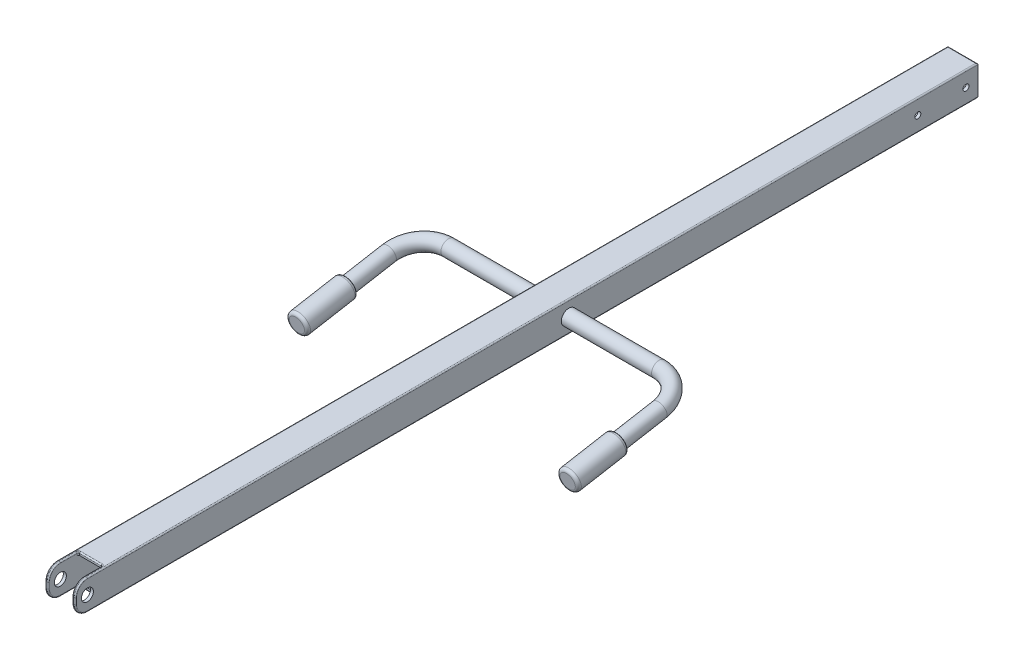
SolidWorks part; units mm, degrees
ref_plane "前视基准面" through (0, 0, 0) normal (0, 0, 1) x (1, 0, 0)
ref_plane "上视基准面" through (0, 0, 0) normal (0, 1, 0) x (1, 0, 0)
ref_plane "右视基准面" through (0, 0, 0) normal (1, 0, 0) x (0, 0, -1)
other "Configuration Table"
sketch "草图1" plane through (0, 0, 0) normal (0, 0, 1) x (1, 0, 0)
  line L1 (-25, 25) -> (25, 25)
  line L2 (-25, 25) -> (-25, -25)
  line L3 (-25, -25) -> (25, -25)
  line L4 (25, 25) -> (25, -25)
  line L5 (-25, 25) -> (25, -25) construction
  line L6 (-25, -25) -> (25, 25) construction
  point P4 (0, 0)
  dimension "D1" = 50
  dimension "D2" = 50
extrude "拉伸-薄壁1" add sketch "草图1" along normal blind 1500 thin thin type one direction reverse wall 5
sketch "草图2" plane through (25, 0, 0) normal (1, 0, 0) x (0, 0, -1)
  line L0 (0, 0) -> (-1500, 0) construction
  line L1 (0, -25) -> (0, 25) construction
  line L2 (-1500, -25) -> (-1500, 25) construction
  line L3 (-1500, 20) -> (-1500, -20) construction
  circle A0 centre (-20, 0) radius 5
  circle A1 centre (-100, 0) radius 5
  circle A2 centre (-1480, 0) radius 10
  dimension "D1" = 10
  dimension "D2" = 20
  dimension "D3" = 80
  dimension "D4" = 20
  dimension "D5" = 20
extrude "切除-拉伸1" cut sketch "草图2" against normal through all
sketch "草图4" plane through (0, 25, 0) normal (0, 1, 0) x (1, 0, 0)
  line L0 (0, -1500) -> (0, -1466.8151) construction
  line L1 (25, -1500) -> (-25, -1500) construction
  line L2 (-25, -1500) -> (-25, 0) construction
  line L3 (20, -1500) -> (-20, -1500)
  line L4 (20, -1500) -> (20, -1450)
  line L5 (20, -1450) -> (-20, -1450)
  line L6 (-20, -1500) -> (-20, -1450)
  line L7 (20, -1500) -> (-20, -1450) construction
  line L8 (20, -1450) -> (-20, -1500) construction
  line L9 (25, -1500) -> (25, 0) construction
  point P8 (0, -1475)
  dimension "D1" = 5
  dimension "D2" = 5
  dimension "D3" = 50
extrude "切除-拉伸2" cut sketch "草图4" against normal through all
fillet "圆角1" radius 20 4 edges at (22.5, -25, 1500) (-22.5, -25, 1500) (-22.5, 25, 1500) (22.5, 25, 1500)
fillet "圆角6" radius 2 28 edges at (25, -19.1421, 1494.1421) (25, 0, 1500) (25, 19.1421, 1494.1421) (20, -19.1421, 1494.1421) (20, 0, 1500) (20, 19.1421, 1494.1421) (-20, -19.1421, 1494.1421) (-20, 0, 1500) (-20, 19.1421, 1494.1421) (-25, -19.1421, 1494.1421) (-25, 0, 1500) (-25, 19.1421, 1494.1421) (0, -25, 0) (-25, -25, 740) (-20, -25, 1465) (0, -25, 1450) (20, -25, 1465) (25, -25, 740) (0, 25, 0) (25, 25, 740) (20, 25, 1465) (0, 25, 1450) (-20, 25, 1465) (-25, 25, 740) (20, -22.5, 1450) (-20, -22.5, 1450) (-20, 22.5, 1450) (20, 22.5, 1450)
sketch "草图7" plane through (0, -25, 0) normal (0, -1, 0) x (1, 0, 0)
  line L0 (0, 0) -> (0, 680) construction
  line L1 (-23, 1480) -> (-25, 1480) construction
  circle A0 centre (0, 680) radius 5
  dimension "D2" = 10
  dimension "D1" = 800
extrude "切除-拉伸3" cut sketch "草图7" against normal blind 10
sketch "草图13" plane through (25, 0, 0) normal (1, 0, 0) x (0, 0, -1)
  line L0 (-680, -23) -> (-680, 23) construction
  line L1 (-1480, -23) -> (0, -23) construction
  line L2 (0, 23) -> (-1480, 23) construction
  line L3 (-685, -25) -> (-675, -25) construction
  line L4 (-685, -25) -> (-675, -25) construction
  circle A0 centre (-680, 0) radius 12.5
  point P8 (-680, -25)
  point P11 (0, 0)
  point P12 (-680, 0)
  dimension "D1" = 25
sketch "草图8" plane through (-25, 0, 0) normal (-1, 0, 0) x (0, 0, 1)
  line L0 (680, 23) -> (680, -23) construction
  line L1 (1480, 23) -> (0, 23) construction
  line L2 (0, -23) -> (1480, -23) construction
  line L3 (675, -25) -> (685, -25) construction
  line L4 (675, -25) -> (685, -25) construction
  circle A0 centre (680, 0) radius 12.5
  circle A1 centre (680, 0) radius 10.5
  point P10 (680, 0)
  point P15 (680, -25)
  dimension "D1" = 25
  dimension "D2" = 2
ref_plane "基准面1" through (0, 116.2868, 20.5045) normal (0, 0.9848, 0.1736) x (1, 0, 0)
sketch "草图9" plane through (0, 116.2868, 20.5045) normal (0, 0.9848, 0.1736) x (1, 0, 0)
  line L0 (-25, -669.6693) -> (-175, -669.6693)
  line L1 (-25, -657.1693) -> (-25, -682.1693) construction
  line L2 (-225, -719.6693) -> (-225, -869.6693)
  arc A0 (-175, -669.6693) -> (-225, -719.6693) centre (-175, -719.6693) ccw
  dimension "D3" = 50
  dimension "D1" = 200
  dimension "D2" = 200
sweep "扫描1" add profiles "草图8" path "草图9"
ref_plane "基准面2" through (0, 0, 0) normal (-1, 0, 0) x (0, 0, 1)
sketch "草图10" plane through (0, -151.0165, 856.457) normal (0, -0.1736, 0.9848) x (1, 0, 0)
  circle A1 centre (-225, 118.0808) radius 12.5
  dimension "D1" = 25
extrude "拉伸-薄壁2" add sketch "草图10" against normal blind 80 thin thin type one direction wall 5
sketch "草图11" plane through (0, -151.0165, 856.457) normal (0, -0.1736, 0.9848) x (1, 0, 0)
  circle A1 centre (-225, 118.0808) radius 17.5
  circle A2 centre (-225, 118.0808) radius 17.5
  dimension "D1" = 0
extrude "凸台-拉伸1" add sketch "草图11" along normal blind 5
fillet "圆角7" radius 5 2 edges at (-207.5, -20.8378, 798.1769) (-225, -52.832, 878.8467)
mirror "镜向1" about plane through (0, 0, 0) normal (-1, 0, 0) of "拉伸-薄壁2", "圆角7", "凸台-拉伸1", "扫描1"
